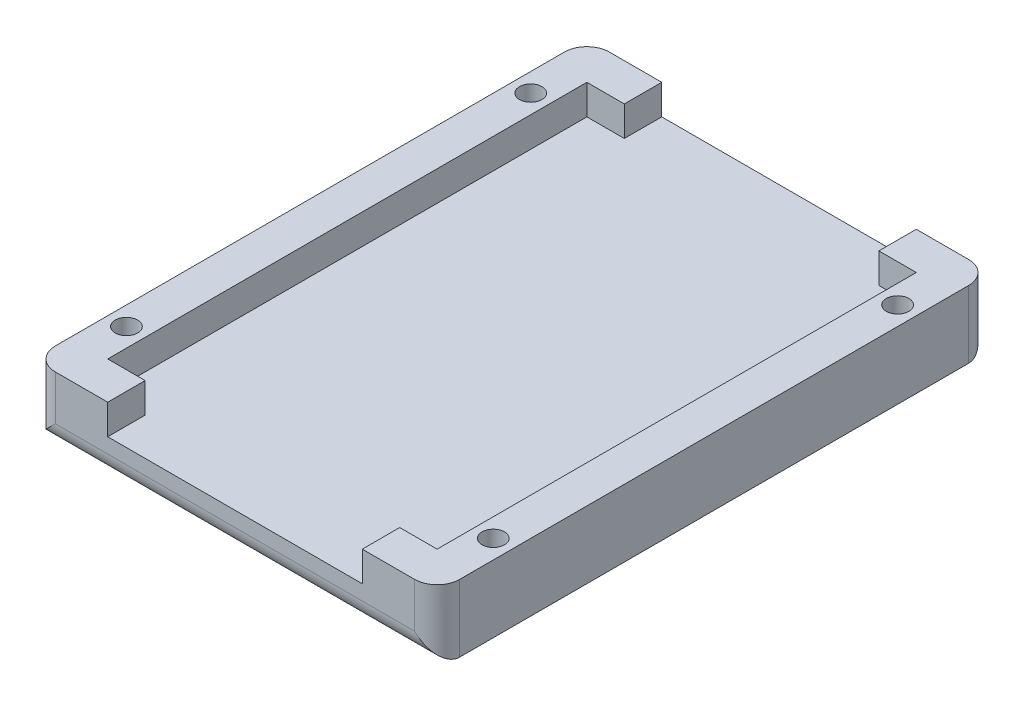
SolidWorks part; units mm, degrees
ref_plane "Plano frontal" through (0, 0, 0) normal (0, 0, 1) x (1, 0, 0)
ref_plane "Plano superior" through (0, 0, 0) normal (0, 1, 0) x (1, 0, 0)
ref_plane "Plano direito" through (0, 0, 0) normal (1, 0, 0) x (0, 0, -1)
sketch "Esboço1" plane through (0, 0, 0) normal (0, 1, 0) x (1, 0, 0)
  line L1 (-27, -37) -> (27, -37)
  line L2 (-27, -37) -> (-27, 37)
  line L3 (-27, 37) -> (27, 37)
  line L4 (27, -37) -> (27, 37)
  line L5 (-27, -37) -> (27, 37) construction
  line L6 (-27, 37) -> (27, -37) construction
  point P0 (0, 0)
  dimension "D1" = 74
  dimension "D2" = 54
extrude "Ressalto-extrusão1" add sketch "Esboço1" along normal blind 5
sketch "Esboço2" plane through (0, 5, 0) normal (0, 1, 0) x (1, 0, 0)
  line L1 (-22, -32) -> (22, -32)
  line L2 (-22, -32) -> (-22, 32)
  line L3 (-22, 32) -> (22, 32)
  line L4 (22, -32) -> (22, 32)
  line L5 (-22, -32) -> (22, 32) construction
  line L6 (-22, 32) -> (22, -32) construction
  line L7 (-27, -37) -> (27, -37)
  line L8 (-27, -37) -> (-27, 37)
  line L9 (-27, 37) -> (27, 37)
  line L10 (27, -37) -> (27, 37)
  line L11 (-27, -37) -> (27, 37) construction
  line L12 (-27, 37) -> (27, -37) construction
  point P0 (0, 0)
  point P6 (0, 0)
  dimension "D1" = 64
  dimension "D2" = 44
extrude "Ressalto-extrusão2" add sketch "Esboço2" along normal blind 4
sketch "Esboço3" plane through (0, 0, 37) normal (0, 0, 1) x (1, 0, 0)
  line L0 (0, 9) -> (0, 5)
  line L1 (-27, 9) -> (27, 9) construction
  line L3 (-17, 5) -> (17, 5)
  line L4 (-17, 5) -> (-17, 9)
  line L5 (-17, 9) -> (17, 9)
  line L6 (17, 5) -> (17, 9)
  line L7 (-17, 5) -> (17, 9) construction
  line L8 (-17, 9) -> (17, 5) construction
  point P5 (0, 7)
  line M8 (27, 9) -> (-27, 9)
  dimension "D1" = 4
  dimension "D2" = 34
extrude "Corte-extrusão1" cut sketch "Esboço3" against normal blind 135.5 contours L4 L3 L0 M8 | L3 L6 L0 M8 region at (8.5, 7, 37) region at (-8.5, 7, 37)
sketch "Esboço5" plane through (0, 9, 0) normal (0, 1, 0) x (1, 0, 0)
  line L0 (27, 0) -> (22, 0) construction
  line L1 (27, -37) -> (27, 37) construction
  line L2 (22, -32) -> (22, 32) construction
  line L3 (24.5, 0) -> (24.5, -37) construction
  line L4 (17, -37) -> (27, -37) construction
  line L5 (24.5, -37) -> (24.5, -27) construction
  circle A0 centre (24.5, -27) radius 1.5
  circle A1 centre (24.5, 27) radius 1.5
  dimension "D2" = 3
  dimension "D1" = 10
extrude "Corte-extrusão2" cut sketch "Esboço5" against normal blind 135.5
sketch "Esboço6" plane through (0, 9, 0) normal (0, 1, 0) x (1, 0, 0)
  line L0 (-27, 0) -> (-22, 0) construction
  line L1 (-27, 37) -> (-27, -37) construction
  line L2 (-22, 32) -> (-22, -32) construction
  line L3 (-24.5, 0) -> (-24.5, -37) construction
  line L4 (-27, -37) -> (-17, -37) construction
  line L5 (-24.5, -37) -> (-24.5, -27) construction
  circle A0 centre (-24.5, -27) radius 1.5
  circle A1 centre (-24.5, 27) radius 1.5
  dimension "D2" = 3
  dimension "D1" = 10
extrude "Corte-extrusão3" cut sketch "Esboço6" against normal blind 135.5
fillet "Filete4" radius 3 6 edges at (27, 4.5, 37) (27, 4.5, -37) (-27, 4.5, -37) (-27, 4.5, 37) (0, 0, 37) (0, 0, -37)
fillet "Filete2" radius 3 rebuild error yes
